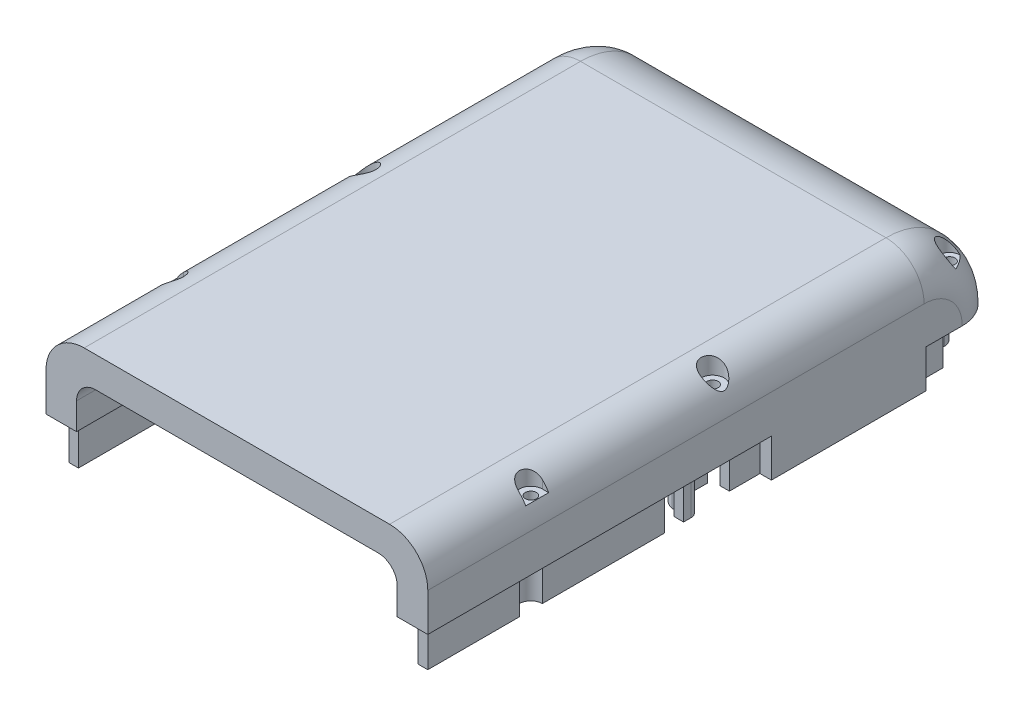
SolidWorks part; units mm, degrees
material "普通碳钢"
ref_plane "Front" through (0, 0, 0) normal (0, 0, 1) x (1, 0, 0)
ref_plane "Top" through (0, 0, 0) normal (0, 1, 0) x (1, 0, 0)
ref_plane "Right" through (0, 0, 0) normal (1, 0, 0) x (0, 0, -1)
sketch "草图1" plane through (0, 0, 0) normal (0, 1, 0) x (1, 0, 0)
  line L5 (50, 75) -> (-50, 75)
  line L6 (50, 75) -> (50, -75)
  line L7 (50, -75) -> (-50, -75)
  line L8 (-50, 75) -> (-50, -75)
  line L9 (50, 75) -> (-50, -75) construction
  line L10 (50, -75) -> (-50, 75) construction
  point P0 (0, 0)
  dimension "D1" = 100
  dimension "D2" = 150
extrude "凸台-拉伸1" add sketch "草图1" along normal blind 20
fillet "圆角4" radius 10 4 edges at (-50, 20, 0) (-50, 10, -75) (50, 10, -75) (50, 20, 0)
fillet "圆角5" radius 20 3 edges at (-47.0711, 17.0711, -72.0711) (47.0711, 17.0711, -72.0711) (0, 20, -75)
shell "抽壳6" thickness 3
sketch "草图5" plane through (0, 0, 0) normal (0, -1, 0) x (1, 0, 0)
  line L0 (47, 72) -> (47, -65) construction
  line L1 (50, -55.5) -> (47, -55.5)
  line L2 (50, -55.5) -> (50, -15)
  line L3 (50, -15) -> (47, -15)
  line L4 (47, -55.5) -> (47, -15)
  line L11 (0, 0) -> (0, -53.9289) construction
  line L12 (-47, -55.5) -> (-47, -15)
  line L13 (-50, -15) -> (-47, -15)
  line L14 (-50, -55.5) -> (-50, -15)
  line L15 (-50, -55.5) -> (-47, -55.5)
  dimension "D1" = 40.5
extrude "凸台-拉伸2" add sketch "草图5" along normal blind 10
sketch "草图6" plane through (0, 0, 0) normal (0, -1, 0) x (1, 0, 0)
  line L0 (47, 72) -> (47, -15) construction
  line L1 (44.5, -63) -> (47, -63)
  line L2 (44.5, -63) -> (44.5, -7)
  line L3 (44.5, -7) -> (47, -7)
  line L4 (47, -63) -> (47, -7)
  line L5 (44.3, -7) -> (47, -7) construction
  line L7 (-44.5, -7) -> (-47, -7)
  line L8 (-44.5, -7) -> (-44.5, -63)
  line L9 (-44.5, -63) -> (-47, -63)
  line L10 (-47, -7) -> (-47, -63)
  line L11 (-44.3, -63) -> (-47, -63) construction
  dimension "D1" = 2.5
  dimension "D2" = 2.5
extrude "凸台-拉伸3" add sketch "草图6" along normal blind 10 and the other way up to next
sketch "草图7" plane through (0, 0, 0) normal (0, -1, 0) x (1, 0, 0)
  line L8 (0, 0) -> (0, -100.1928) construction
  line L16 (-38.3, -69.5) -> (38.3, -69.5)
  line L17 (-38.8, -63.5) -> (-41.3, -63.5)
  line L27 (-31.6, -61) -> (-31.6, -58.5)
  line L30 (-38.8, -69) -> (-38.8, -63.5)
  line L31 (-31.6, -61) -> (-11.1, -61)
  line L32 (-11.1, -61) -> (-11.1, -9.5)
  line L36 (-31.6, -9.5) -> (-31.6, -12)
  line L37 (-11.1, -9.5) -> (-31.6, -9.5)
  line L42 (-47, -7) -> (-47, 72) construction
  line L46 (-31.6, -12) -> (-13.6, -12)
  line L47 (-13.6, -12) -> (-13.6, -58.5)
  line L48 (-13.6, -58.5) -> (-31.6, -58.5)
  line L49 (-41.3, -63.5) -> (-41.3, -69)
  line L67 (-47, 10.0516) -> (-44.5, 10)
  line L68 (-44.5, 10) -> (-44.5, 40.101)
  line L69 (-47, 10.0516) -> (-47, 39.5)
  line L70 (-47, 50.5) -> (-47, 72)
  line L71 (-47, 72) -> (47, 72) construction
  line L72 (-47, 72) -> (-44.5, 72)
  line L73 (-44.5, 72) -> (-44.5, 49.899)
  line L74 (-47, 50.5) -> (-47, 48)
  line L75 (-47, 42) -> (-47, 39.5)
  line L76 (47, 42) -> (47, 39.5)
  line L77 (47, 50.5) -> (47, 48)
  line L78 (44.5, 69) -> (44.5, 49.899)
  line L79 (47, 72) -> (44.5, 72)
  line L80 (47, 50.5) -> (47, 72)
  line L81 (47, 10.0516) -> (47, 39.5)
  line L82 (44.5, 10) -> (44.5, 40.101)
  line L83 (47, 10.0516) -> (44.5, 10)
  line L84 (41.3, -63.5) -> (41.3, -69)
  line L85 (13.6, -58.5) -> (31.6, -58.5)
  line L86 (13.6, -12) -> (13.6, -58.5)
  line L87 (31.6, -12) -> (13.6, -12)
  line L95 (11.1, -9.5) -> (31.6, -9.5)
  line L96 (31.6, -9.5) -> (31.6, -12)
  line L97 (11.1, -61) -> (11.1, -9.5)
  line L98 (31.6, -61) -> (11.1, -61)
  line L99 (38.8, -69) -> (38.8, -63.5)
  line L101 (31.6, -61) -> (31.6, -58.5)
  line L102 (38.8, -63.5) -> (41.3, -63.5)
  line L111 (44.5, 69) -> (44.5, 72)
  line L112 (38.3, -72) -> (-38.3, -72)
  line L117 (47, 3) -> (47, 5)
  line L118 (41.3, -1) -> (41.3, -7)
  line L119 (41.3, -7) -> (38.8, -7)
  line L120 (38.8, -7) -> (38.8, -1)
  line L121 (43.3, 1) -> (45, 1)
  line L122 (47, 5) -> (44.4486, 5)
  line L123 (-47, 5) -> (-44.4486, 5)
  line L124 (-43.3, 1) -> (-45, 1)
  line L125 (-38.8, -7) -> (-38.8, -1)
  line L126 (-41.3, -7) -> (-38.8, -7)
  line L127 (-41.3, -1) -> (-41.3, -7)
  line L128 (-47, 3) -> (-47, 5)
  arc A0 (-47, 42) -> (-47, 48) centre (-47, 45) ccw
  arc A15 (-38.8, -69) -> (-38.3, -69.5) centre (-38.3, -69) ccw
  arc A18 (-44.5, 40.101) -> (-44.5, 49.899) centre (-47, 45) ccw
  arc A19 (44.5, 40.101) -> (44.5, 49.899) centre (47, 45) cw
  arc A22 (38.8, -69) -> (38.3, -69.5) centre (38.3, -69) cw
  arc A27 (47, 42) -> (47, 48) centre (47, 45) cw
  arc A33 (-41.3, -69) -> (-38.3, -72) centre (-38.3, -69) ccw
  arc A34 (38.3, -72) -> (41.3, -69) centre (38.3, -69) ccw
  arc A35 (45, 1) -> (47, 3) centre (45, 3) ccw
  arc A36 (43.3, 1) -> (41.3, -1) centre (43.3, -1) ccw
  arc A37 (43.0619, 3.4937) -> (38.8, -1) centre (43.3, -1) ccw
  arc A38 (42.4332, 3.4157) -> (44.4855, 5) centre (42.5, 5.4506) ccw
  arc A39 (-42.4332, 3.4157) -> (-44.4855, 5) centre (-42.5, 5.4506) cw
  arc A40 (-43.0619, 3.4937) -> (-38.8, -1) centre (-43.3, -1) cw
  arc A41 (-43.3, 1) -> (-41.3, -1) centre (-43.3, -1) cw
  arc A42 (-45, 1) -> (-47, 3) centre (-45, 3) cw
  point P26 (0, -72)
  point P36 (0, -69.5)
  point P55 (0, -69.5)
  line M5 (-47, -7) -> (-47, 72)
  line M6 (-47, 72) -> (47, 72)
  line M7 (47, 72) -> (47, -7)
extrude "凸台-拉伸4" add sketch "草图7" along normal blind 11 and the other way up to next contours L68 A18 L73 A0 L67 M6 M5 | A27 L111 L78 A19 L82 L83 M7 M6 | A38 A37 L120 L119 L118 A36 L121 A35 L122 M7 | A42 L124 A41 L127 L126 L125 A40 A39 L123 M5 | L47 L48 L27 L31 L32 L37 L36 L46 | L98 L101 L85 L86 L87 L96 L95 L97 | L16 L8 L112 A34 L84 L102 L99 A22 | L8 L16 A15 L30 L17 L49 A33 L112
sketch "草图23" plane through (0, 0, 0) normal (0, -1, 0) x (-1, 0, 0)
  line L1 (-47, -48) -> (-47, -42) construction
  circle A0 centre (47, -45) radius 3
  circle A1 centre (-47, -45) radius 3
extrude "凸台-拉伸13" add sketch "草图23" against normal up to body
sketch "草图9" plane through (0, 0, 0) normal (0, -1, 0) x (-1, 0, 0)
  line L4 (-47, -3) -> (-47, 7) construction
  line L5 (-47, -3) -> (-47, 7)
  line L6 (-42.8, 15) -> (-44.5, 15)
  line L7 (-44.5, 7) -> (-44.5, 63) construction
  line L8 (-44.5, 15) -> (-44.5, 7)
  line L9 (-44.5, 7) -> (-47, 7)
  line L11 (-40.8, 13) -> (-40.8, 1)
  line L12 (-42.8, -1) -> (-45, -1)
  line L13 (-45, -1) -> (-43.3, -1) construction
  line L14 (0, 0) -> (0, 18.6927)
  line L15 (42.8, -1) -> (45, -1)
  line L16 (40.8, 13) -> (40.8, 1)
  line L17 (44.5, 7) -> (47, 7)
  line L18 (44.5, 15) -> (44.5, 7)
  line L19 (42.8, 15) -> (44.5, 15)
  line L20 (47, -3) -> (47, 7)
  circle A0 centre (-47, -45) radius 3
  circle A1 centre (47, -45) radius 3
  arc A2 (-45, -1) -> (-47, -3) centre (-45, -3) ccw
  arc A3 (-40.8, 1) -> (-42.8, -1) centre (-42.8, 1) cw
  arc A4 (40.8, 1) -> (42.8, -1) centre (42.8, 1) ccw
  arc A5 (45, -1) -> (47, -3) centre (45, -3) cw
  arc A6 (-42.8, 15) -> (-40.8, 13) centre (-42.8, 13) cw
  arc A7 (42.8, 15) -> (40.8, 13) centre (42.8, 13) ccw
  point P46 (-40.8, 15)
  point P49 (40.8, 15)
  dimension "D1" = 2
  dimension "D2" = 2
  dimension "D3" = 2
extrude "凸台-拉伸5" add sketch "草图9" against normal up to body
sketch "草图10" plane through (0, 0, 0) normal (0, -1, 0) x (1, 0, 0)
  line L3 (-40, -72) -> (-40, -62)
  line L4 (-42, -60) -> (-44.5, -60)
  line L7 (-44.5, -60) -> (-44.5, -63)
  line L10 (-44.5, -63) -> (-47, -63)
  line L11 (-47, -63) -> (-47, -65)
  line L12 (0, 0) -> (0, -94.4608) construction
  line L13 (47, -63) -> (47, -65)
  line L14 (44.5, -63) -> (47, -63)
  line L15 (44.5, -60) -> (44.5, -63)
  line L16 (42, -60) -> (44.5, -60)
  line L17 (40, -72) -> (40, -62)
  line L18 (-47, -65) -> (-47, -72)
  line L19 (-47, -72) -> (-40, -72)
  line L20 (47, -65) -> (47, -72)
  line L21 (47, -72) -> (40, -72)
  arc A2 (-40, -62) -> (-42, -60) centre (-42, -62) ccw
  arc A6 (40, -62) -> (42, -60) centre (42, -62) cw
  point P27 (-40, -60)
  point P36 (40, -60)
  dimension "D1" = 2
extrude "凸台-拉伸6" add sketch "草图10" against normal up to body
sketch "草图11" plane through (0, 0, 0) normal (0, -1, 0) x (1, 0, 0)
  circle A0 centre (-45.65, -66) radius 1.45
  circle A1 centre (-45.6051, -4) radius 1.45
  circle A2 centre (-47, 45) radius 1.45
  circle A3 centre (47, 45) radius 1.45
  circle A4 centre (45.6051, -4) radius 1.45
  circle A5 centre (45.65, -66) radius 1.45
  dimension "D1" = 2.9
extrude "切除-拉伸1" cut sketch "草图11" against normal through all and the other way blind 10
sketch "草图13" plane through (0, 0, 75) normal (0, 0, 1) x (1, 0, 0)
  line L0 (-50, 0) -> (50, 0) construction
  line L5 (-42, 0) -> (42, 0)
  line L6 (-42, 0) -> (-42, 7)
  line L7 (-37, 12) -> (37, 12)
  line L16 (42, 0) -> (42, 7)
  line L18 (50, 10) -> (50, 0) construction
  line L19 (-50, 10) -> (-50, 0) construction
  arc A4 (42, 7) -> (37, 12) centre (37, 7) ccw
  arc A5 (-37, 12) -> (-42, 7) centre (-37, 7) ccw
  dimension "D4" = 5
  dimension "D2" = 8
  dimension "D3" = 8
sketch "草图14" plane through (0, 0, 75) normal (0, 0, 1) x (1, 0, 0)
  line L22 (-42, 0) -> (-42, 7)
  line L23 (-37, 12) -> (37, 12)
  line L24 (42, 0) -> (42, 7)
  line L25 (-50, 0) -> (50, 0) construction
  line L28 (40.5, 1.5) -> (40.5, 7)
  line L29 (-37, 10.5) -> (37, 10.5)
  line L30 (-40.5, 1.5) -> (-40.5, 7)
  line L34 (-42, 0) -> (42, 0) construction
  line L35 (-40.5, 1.5) -> (40.5, 1.5) construction
  line L46 (-42, 0) -> (-40.5, 0)
  line L47 (-42, 0) -> (-40, 0) construction
  line L48 (-40.5, 0) -> (-40.5, 1.5)
  line L50 (40.5, 1.5) -> (40.5, 0)
  line L52 (40, 0) -> (42, 0) construction
  line L53 (40.5, 0) -> (42, 0)
  arc A4 (37, 12) -> (42, 7) centre (37, 7) cw
  arc A5 (-37, 12) -> (-42, 7) centre (-37, 7) ccw
  arc A6 (37, 10.5) -> (40.5, 7) centre (37, 7) cw
  arc A7 (-37, 10.5) -> (-40.5, 7) centre (-37, 7) ccw
  dimension "D2" = 1.5
  dimension "D1" = 5
extrude "凸台-拉伸7" add sketch "草图14" along normal blind 10
sketch "草图15" plane through (0, 20, 0) normal (0, 1, 0) x (1, 0, 0)
  line L0 (-47, -42) -> (-50, -42)
  line L2 (-50, -42) -> (-50, -48)
  line L3 (-50, -48) -> (-47, -48)
  line L4 (47, -42) -> (50, -42)
  line L6 (50, -42) -> (50, -48)
  line L7 (50, -48) -> (47, -48)
  circle A2 centre (45.6051, 4) radius 3
  arc A3 (47, -42) -> (47, -48) centre (47, -45) ccw
  arc A4 (-47, -48) -> (-47, -42) centre (-47, -45) ccw
  circle A5 centre (-45.6051, 4) radius 3
  dimension "D1" = 6
extrude "切除-拉伸4" cut sketch "草图15" against normal blind 5
sketch "草图16" plane through (0, 20, 0) normal (0, 1, 0) x (1, 0, 0)
  circle A0 centre (-45.65, 66) radius 2.8
  circle A1 centre (45.65, 66) radius 2.8
  dimension "D1" = 5.6
extrude "切除-拉伸5" cut sketch "草图16" against normal blind 8
ref_plane "基准面1" through (0, -9, 0) normal (0, -1, 0) x (-1, 0, 0)
sketch "草图22" plane through (0, -9, 0) normal (0, -1, 0) x (-1, 0, 0)
  line L0 (0, 0) -> (0, 84.2923) construction
  line L1 (44.5, 15) -> (41.3, 15)
  line L2 (44.5, 15) -> (44.5, 55.4694)
  line L3 (44.5, 55.4694) -> (41.3, 55.4694)
  line L5 (41.3, 58.5) -> (13.6, 58.5)
  line L6 (41.3, 58.5) -> (41.3, 55.4694)
  line L7 (41.3, 12) -> (13.6, 12)
  line L8 (13.6, 58.5) -> (13.6, 12)
  line L17 (41.3, 15) -> (41.3, 12)
  line L18 (-41.3, 15) -> (-41.3, 12)
  line L19 (-13.6, 58.5) -> (-13.6, 12)
  line L20 (-41.3, 12) -> (-13.6, 12)
  line L21 (-41.3, 58.5) -> (-41.3, 55.4694)
  line L22 (-41.3, 58.5) -> (-13.6, 58.5)
  line L23 (-44.5, 55.4694) -> (-41.3, 55.4694)
  line L24 (-44.5, 15) -> (-44.5, 55.4694)
  line L25 (-44.5, 15) -> (-41.3, 15)
  line L26 (-44.5, 7) -> (-44.5, 63) construction
extrude "凸台-拉伸11" add sketch "草图22" against normal blind 3
sketch "草图21" plane through (0, 0, -61) normal (0, 0, -1) x (-1, 0, 0)
  line L0 (42, 0) -> (-42, 0) construction
  line L1 (-27.25, 0) -> (-25.75, 0)
  line L2 (-27.25, 0) -> (-27.25, -16.9865)
  line L3 (-27.25, -16.9865) -> (-25.75, -16.9865)
  line L4 (-25.75, 0) -> (-25.75, -16.9865)
  line L5 (25.75, -18.55) -> (27.25, -18.55)
  line L6 (25.75, -18.55) -> (25.75, 0)
  line L7 (25.75, 0) -> (27.25, 0)
  line L8 (27.25, -18.55) -> (27.25, 0)
extrude "凸台-拉伸10" add sketch "草图21" along normal blind 1.5
sketch "草图27" plane through (0, 17, 0) normal (0, -1, 0) x (-1, 0, 0)
  line L0 (4, -16) -> (-5, -16)
  line L1 (1, -13) -> (-17, -13)
  line L2 (1, -13) -> (1, -3)
  line L3 (1, -3) -> (-17, -3)
  line L4 (-17, -13) -> (-17, -3)
  line L5 (-20, -16) -> (-20, 0)
  line L6 (4, 0) -> (-20, 0)
  line L7 (4, -16) -> (4, -10.5612)
  line L8 (4, -5.4388) -> (4, 0)
  line L9 (12, -8) -> (12, -63.1153) construction
  line L10 (4, -16) -> (4, 0) construction
  line L11 (-8, 0) -> (-8, -64.4449) construction
  line L13 (15, -21) -> (9, -21)
  line L14 (15, -21) -> (15, -15.846)
  line L16 (9, -21) -> (9, -15.846)
  line L17 (-11, -16) -> (-20, -16)
  line L18 (-5, -21) -> (-11, -21)
  line L19 (-5, -21) -> (-5, -16)
  line L21 (-11, -21) -> (-11, -16)
  line L23 (4, -16) -> (-20, -16) construction
  circle A0 centre (12, -8) radius 5.4
  arc A1 (4, -10.5612) -> (9, -15.846) centre (12, -8) ccw
  arc A2 (15, -15.846) -> (4, -5.4388) centre (12, -8) ccw
  circle A3 centre (12, -8) radius 8.4 construction
  point P15 (20.4, -45)
  dimension "D2" = 6
  dimension "D3" = 6
  dimension "D1" = 3
extrude "凸台-拉伸16" add sketch "草图27" along normal blind 10
sketch "草图28" plane through (0, 0, 21) normal (0, 0, 1) x (1, 0, 0)
  line L0 (-12, 7) -> (-12, 15.6796) construction
  line L1 (-9, 7) -> (-15, 7) construction
  line L2 (-12, 7) -> (-12, 15.3377) construction
  line L3 (-9, 7) -> (-15, 7) construction
  circle A0 centre (-12, 12) radius 1.3654
  circle A1 centre (-12, 12) radius 1.3698
  dimension "D1" = 5
  dimension "D2" = 5
extrude "切除-拉伸9" cut sketch "草图28" against normal up to next
fillet "圆角3" radius 1 21 edges at (-4, 12, 5.4388) (-4, 12, 10.5612) (17, 7, 8) (8, 7, 13) (-1, 7, 8) (8, 7, 3) (-12, 7, 2.6) (0.5, 7, 16) (5, 7, 18.5) (-12, 7, 21) (11, 7, 18.5) (15.5, 7, 16) (20, 7, 8) (8, 7, 0) (-4, 7, 2.7194) (-17.773, 7, 1.8982) (-15, 7, 18.423) (-9, 7, 18.423) (-5.8982, 7, 13.773) (-4, 7, 13.2806) (8, 7, 21)
extrude "切除-拉伸11" cut sketch "草图13" along normal blind 20 and the other way up to next
sketch "草图30" plane through (0, 0, 72) normal (0, 0, -1) x (-1, 0, 0)
  line L0 (-43.5, 0) -> (-43.5, 7)
  line L1 (-37, 13.5) -> (37, 13.5)
  line L2 (43.5, 7) -> (43.5, 0)
  line L3 (-43.5, 0) -> (-42, 0)
  line L4 (42, 0) -> (43.5, 0)
  line L5 (42, 7) -> (42, 0) construction
  line L6 (42, 7) -> (42, 0)
  line L7 (-37, 12) -> (37, 12) construction
  line L8 (-37, 12) -> (37, 12)
  line L9 (-42, 0) -> (-42, 7) construction
  line L10 (-42, 0) -> (-42, 7)
  arc A0 (-37, 13.5) -> (-43.5, 7) centre (-37, 7) ccw
  arc A1 (43.5, 7) -> (37, 13.5) centre (37, 7) ccw
  arc A2 (42, 7) -> (37, 12) centre (37, 7) ccw construction
  arc A3 (42, 7) -> (37, 12) centre (37, 7) ccw
  arc A4 (-37, 12) -> (-42, 7) centre (-37, 7) ccw construction
  arc A5 (-37, 12) -> (-42, 7) centre (-37, 7) ccw
extrude "凸台-拉伸18" add sketch "草图30" along normal blind 10
sketch "草图31" plane through (0, -11, 0) normal (0, -1, 0) x (1, 0, 0)
  line L0 (27.25, -61) -> (31.6, -61) construction
  line L1 (31.6, -61) -> (31.6, -58.5) construction
  line L2 (31.6, -58.5) -> (13.6, -58.5) construction
  line L3 (13.6, -58.5) -> (13.6, -12) construction
  line L4 (13.6, -12) -> (31.6, -12) construction
  line L5 (31.6, -12) -> (31.6, -9.5) construction
  line L6 (31.6, -9.5) -> (11.1, -9.5) construction
  line L7 (11.1, -9.5) -> (11.1, -61) construction
  line L8 (11.1, -61) -> (25.75, -61) construction
  line L9 (25.75, -61) -> (27.25, -61) construction
  line L10 (-13.6, -12) -> (-13.6, -58.5) construction
  line L11 (-13.6, -58.5) -> (-31.6, -58.5) construction
  line L12 (-31.6, -58.5) -> (-31.6, -61) construction
  line L13 (-31.6, -61) -> (-27.25, -61) construction
  line L14 (-27.25, -61) -> (-25.75, -61) construction
  line L15 (-25.75, -61) -> (-11.1, -61) construction
  line L16 (-11.1, -61) -> (-11.1, -9.5) construction
  line L17 (-11.1, -9.5) -> (-31.6, -9.5) construction
  line L18 (-31.6, -9.5) -> (-31.6, -12) construction
  line L19 (-31.6, -12) -> (-13.6, -12) construction
  line L20 (27.25, -61) -> (31.6, -61)
  line L21 (31.6, -61) -> (31.6, -58.5)
  line L22 (31.6, -58.5) -> (13.6, -58.5)
  line L23 (13.6, -58.5) -> (13.6, -12)
  line L24 (13.6, -12) -> (31.6, -12)
  line L25 (31.6, -12) -> (31.6, -9.5)
  line L26 (31.6, -9.5) -> (11.1, -9.5)
  line L27 (11.1, -9.5) -> (11.1, -61)
  line L28 (11.1, -61) -> (25.75, -61)
  line L29 (25.75, -61) -> (27.25, -61)
  line L30 (-13.6, -12) -> (-13.6, -58.5)
  line L31 (-13.6, -58.5) -> (-31.6, -58.5)
  line L32 (-31.6, -58.5) -> (-31.6, -61)
  line L33 (-31.6, -61) -> (-27.25, -61)
  line L34 (-27.25, -61) -> (-25.75, -61)
  line L35 (-25.75, -61) -> (-11.1, -61)
  line L36 (-11.1, -61) -> (-11.1, -9.5)
  line L37 (-11.1, -9.5) -> (-31.6, -9.5)
  line L38 (-31.6, -9.5) -> (-31.6, -12)
  line L39 (-31.6, -12) -> (-13.6, -12)
extrude "切除-拉伸12" cut sketch "草图31" against normal blind 1
